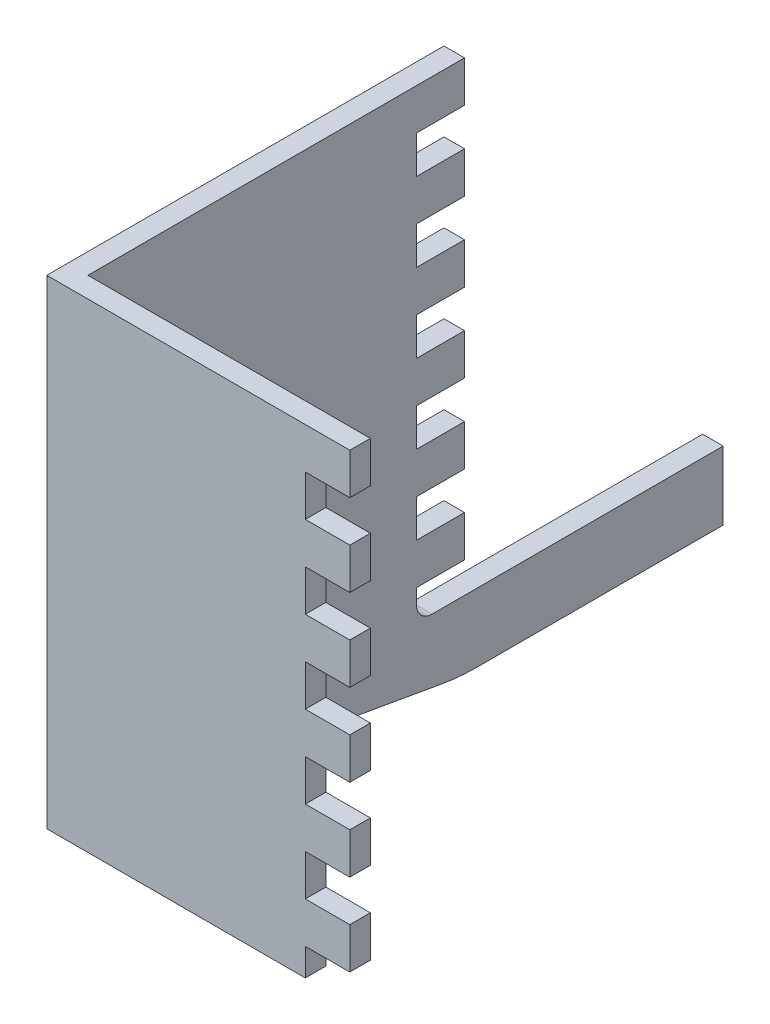
SolidWorks part; units mm, degrees
ref_plane "Alzado" through (0, 0, 0) normal (0, 0, 1) x (1, 0, 0)
ref_plane "Planta" through (0, 0, 0) normal (0, 1, 0) x (1, 0, 0)
ref_plane "Vista lateral" through (0, 0, 0) normal (1, 0, 0) x (0, 0, -1)
sketch "Croquis1" plane through (0, 0, 0) normal (0, 0, 1) x (1, 0, 0)
  line L1 (18.875, 35) -> (-18.875, 35)
  line L2 (18.875, 35) -> (18.875, -35)
  line L3 (18.875, -35) -> (-18.875, -35)
  line L4 (-18.875, 35) -> (-18.875, -35)
  line L5 (18.875, 35) -> (-18.875, -35) construction
  line L6 (18.875, -35) -> (-18.875, 35) construction
  point P0 (0, 0)
  dimension "D1" = 70
  dimension "D2" = 37.75
extrude "Saliente-Extruir1" add sketch "Croquis1" along normal blind 3
sketch "Croquis2" plane through (0, 0, 0) normal (0, 0, -1) x (-1, 0, 0)
  line L0 (18.875, -35) -> (-18.875, -35) construction
  line L1 (18.875, 35) -> (15.875, 35)
  line L2 (18.875, 35) -> (18.875, -35)
  line L3 (18.875, -35) -> (15.875, -35)
  line L4 (15.875, 35) -> (15.875, -35)
  dimension "D1" = 3
extrude "Saliente-Extruir2" add sketch "Croquis2" along normal blind 30
sketch "Croquis3" plane through (18.875, 0, 0) normal (1, 0, 0) x (0, 0, -1)
  line L0 (-1.5, 35) -> (-1.5, -35) construction
  line L1 (-3, 35) -> (0, 35) construction
  line L2 (-3, -35) -> (0, -35) construction
  line L3 (0, 17) -> (-3, 17)
  line L4 (0, 29) -> (-3, 29)
  line L5 (0, 29) -> (0, 35)
  line L6 (0, 35) -> (-3, 35)
  line L7 (-3, 29) -> (-3, 35)
  line L8 (0, 29) -> (-3, 35) construction
  line L9 (0, 35) -> (-3, 29) construction
  line L10 (0, 17) -> (0, 23)
  line L11 (0, 23) -> (-3, 23)
  line L12 (-3, 17) -> (-3, 23)
  line L13 (0, 17) -> (-3, 23) construction
  line L14 (0, 23) -> (-3, 17) construction
  line L15 (0, 5) -> (-3, 5)
  line L16 (0, 5) -> (0, 11)
  line L17 (0, 11) -> (-3, 11)
  line L18 (-3, 5) -> (-3, 11)
  line L19 (0, 5) -> (-3, 11) construction
  line L20 (0, 11) -> (-3, 5) construction
  line L21 (0, -7) -> (-3, -7)
  line L22 (0, -7) -> (0, -1)
  line L23 (0, -1) -> (-3, -1)
  line L24 (-3, -7) -> (-3, -1)
  line L25 (0, -7) -> (-3, -1) construction
  line L26 (0, -1) -> (-3, -7) construction
  line L27 (0, -19) -> (-3, -19)
  line L28 (0, -19) -> (0, -13)
  line L29 (0, -13) -> (-3, -13)
  line L30 (-3, -19) -> (-3, -13)
  line L31 (0, -19) -> (-3, -13) construction
  line L32 (0, -13) -> (-3, -19) construction
  line L33 (0, -31) -> (-3, -31)
  line L34 (0, -31) -> (0, -25)
  line L35 (0, -25) -> (-3, -25)
  line L36 (-3, -31) -> (-3, -25)
  line L37 (0, -31) -> (-3, -25) construction
  line L38 (0, -25) -> (-3, -31) construction
  line L45 (-3, 35) -> (0, 35) construction
  dimension "D1" = 6
  dimension "D3" = 3
  dimension "D4" = 6
extrude "Saliente-Extruir3" add sketch "Croquis3" along normal blind 6.5
sketch "Croquis4" plane through (-15.875, 0, 0) normal (1, 0, 0) x (0, 0, -1)
  line L0 (30, 35) -> (30, -35) construction
  line L1 (30, 35) -> (55, 35)
  line L2 (30, 35) -> (30, -35)
  line L3 (30, -35) -> (55, -35)
  line L4 (55, 35) -> (55, -35)
  line L5 (30, -35) -> (0, -35) construction
  dimension "D1" = 70
  dimension "D2" = 0
  dimension "D3" = 25
extrude "Saliente-Extruir5" add sketch "Croquis4" against normal blind 3
sketch "Croquis5" plane through (0, 0, -55) normal (0, 0, -1) x (-1, 0, 0)
  line L3 (15.875, 29) -> (18.875, 29)
  line L4 (15.875, 35) -> (15.875, -35)
  line L5 (15.875, -35) -> (18.875, -35)
  line L6 (18.875, -35) -> (18.875, 35)
  line L7 (18.875, 35) -> (15.875, 35)
  line L8 (15.875, 35) -> (15.875, -35) construction
  line L9 (15.875, -35) -> (18.875, -35) construction
  line L10 (18.875, -35) -> (18.875, 35) construction
  line L11 (18.875, 35) -> (15.875, 35) construction
  line L12 (18.875, 29) -> (18.875, 23.5)
  line L13 (18.875, 23.5) -> (15.875, 23.5)
  line L14 (15.875, 23.5) -> (15.875, 29)
  line L15 (15.875, 17.5) -> (18.875, 17.5)
  line L16 (18.875, 17.5) -> (18.875, 12)
  line L17 (18.875, 12) -> (15.875, 12)
  line L18 (15.875, 12) -> (15.875, 17.5)
  line L19 (15.875, 6) -> (18.875, 6)
  line L20 (18.875, 6) -> (18.875, 0.5)
  line L21 (18.875, 0.5) -> (15.875, 0.5)
  line L22 (15.875, 0.5) -> (15.875, 6)
  line L23 (15.875, -5.5) -> (18.875, -5.5)
  line L24 (18.875, -5.5) -> (18.875, -11)
  line L25 (18.875, -11) -> (15.875, -11)
  line L26 (15.875, -11) -> (15.875, -5.5)
  line L27 (15.875, -17) -> (18.875, -17)
  line L28 (18.875, -17) -> (18.875, -22.5)
  line L29 (18.875, -22.5) -> (15.875, -22.5)
  line L30 (15.875, -22.5) -> (15.875, -17)
  dimension "D2" = 5.5
  dimension "D3" = 6
  dimension "D1" = 0
  dimension "D4" = 5
extrude "Cortar-Extruir1" cut sketch "Croquis5" against normal blind 7
sketch "Croquis6" plane through (-18.875, 0, 0) normal (-1, 0, 0) x (0, 0, 1)
  line L2 (-48, 35.7325) -> (-48, -30.7325)
  line L3 (-50.25, -32.9825) -> (-92.775, -32.9825)
  arc A1 (-50.25, -32.9825) -> (-48, -30.7325) centre (-50.25, -30.7325) ccw
sketch "Croquis7" plane through (-18.875, 0, 0) normal (-1, 0, 0) x (0, 0, 1)
  line L0 (3, 35) -> (3, -35) construction
  line L1 (3, 35) -> (3, -35) construction
  line L2 (3, -35) -> (-55, -35) construction
  line L3 (3, -35) -> (-55, -35) construction
  line L4 (-9, -35) -> (-51.6862, -42.5267)
  line L5 (-50.25, -32.9825) -> (-92.775, -32.9825) construction
  line L6 (-50.25, -32.9825) -> (-92.775, -32.9825)
  line L7 (-92.775, -32.9825) -> (-92.775, -42.9825)
  line L8 (-92.775, -42.9825) -> (-56.8957, -42.9825)
  line L9 (-50.25, -32.9825) -> (-9, -35)
  arc A0 (-51.6862, -42.5267) -> (-56.8957, -42.9825) centre (-56.8957, -12.9825) cw
  dimension "D4" = 30
  dimension "D1" = 12
  dimension "D2" = 10
  dimension "D3" = 10
extrude "Saliente-Extruir6" add sketch "Croquis7" against normal blind 3
sketch "Croquis8" plane through (-18.875, 0, 0) normal (-1, 0, 0) x (0, 0, 1)
  line L0 (-48, 35.7325) -> (-48, -30.7325) construction
  line L1 (-50.25, -32.9825) -> (-92.775, -32.9825) construction
  line L2 (-48, -28.5) -> (-48, -30.7325)
  line L3 (-50.25, -32.9825) -> (-92.775, -32.9825)
  line L4 (-48, -22.5) -> (-55, -22.5) construction
  line L5 (-48, -22.5) -> (-55, -22.5) construction
  line L6 (-48, -28.5) -> (-92.775, -28.5)
  line L7 (-92.775, -28.5) -> (-92.775, -32.9825)
  arc A0 (-50.25, -32.9825) -> (-48, -30.7325) centre (-50.25, -30.7325) ccw construction
  arc A1 (-50.25, -32.9825) -> (-48, -30.7325) centre (-50.25, -30.7325) ccw
  dimension "D1" = 6
extrude "Cortar-Extruir2" cut sketch "Croquis8" against normal through all both and the other way through all
